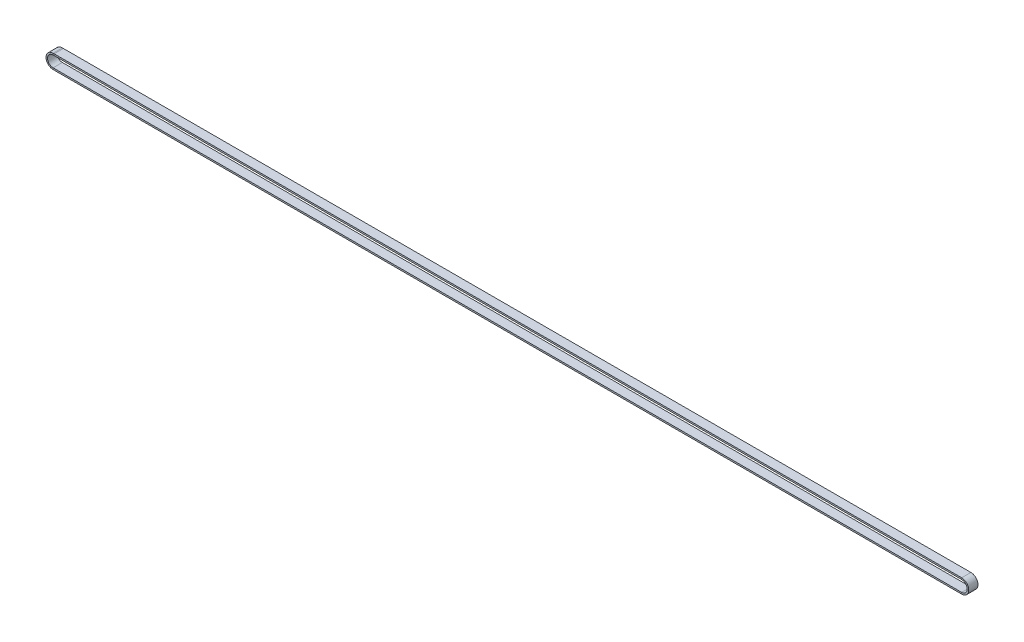
SolidWorks part; units mm, degrees
ref_plane "Front Plane" through (0, 0, 0) normal (0, 0, 1) x (1, 0, 0)
ref_plane "Top Plane" through (0, 0, 0) normal (0, 1, 0) x (1, 0, 0)
ref_plane "Right Plane" through (0, 0, 0) normal (1, 0, 0) x (0, 0, -1)
sketch "Sketch2" plane through (0, 0, -110.2334) normal (0, 0, 1) x (1, 0, 0)
  line L0 (0, 0) -> (1, 0) construction
  line L1 (0, 0) -> (0, 1) construction
  line L2 (-1, 48.8431) -> (883.5206, 48.8431)
  line L3 (883.5206, 35.0431) -> (-1, 35.0431)
  arc A0 (-1, 35.0431) -> (-1, 48.8431) centre (-1, 41.9431) cw
  arc A1 (883.5206, 48.8431) -> (883.5206, 35.0431) centre (883.5206, 41.9431) cw
sketch "Sketch3" plane through (0, 0, 0) normal (1, 0, 0) x (0, 0, -1)
  line L1 (110.2334, 47.3431) -> (101.2334, 47.3431)
  line L2 (110.2334, 47.3431) -> (110.2334, 48.8431)
  line L3 (110.2334, 48.8431) -> (101.2334, 48.8431)
  line L4 (101.2334, 47.3431) -> (101.2334, 48.8431)
  dimension "D1" = 9
  dimension "D2" = 1.5
sweep "Sweep1" add profiles "Sketch3" path "Sketch2"
